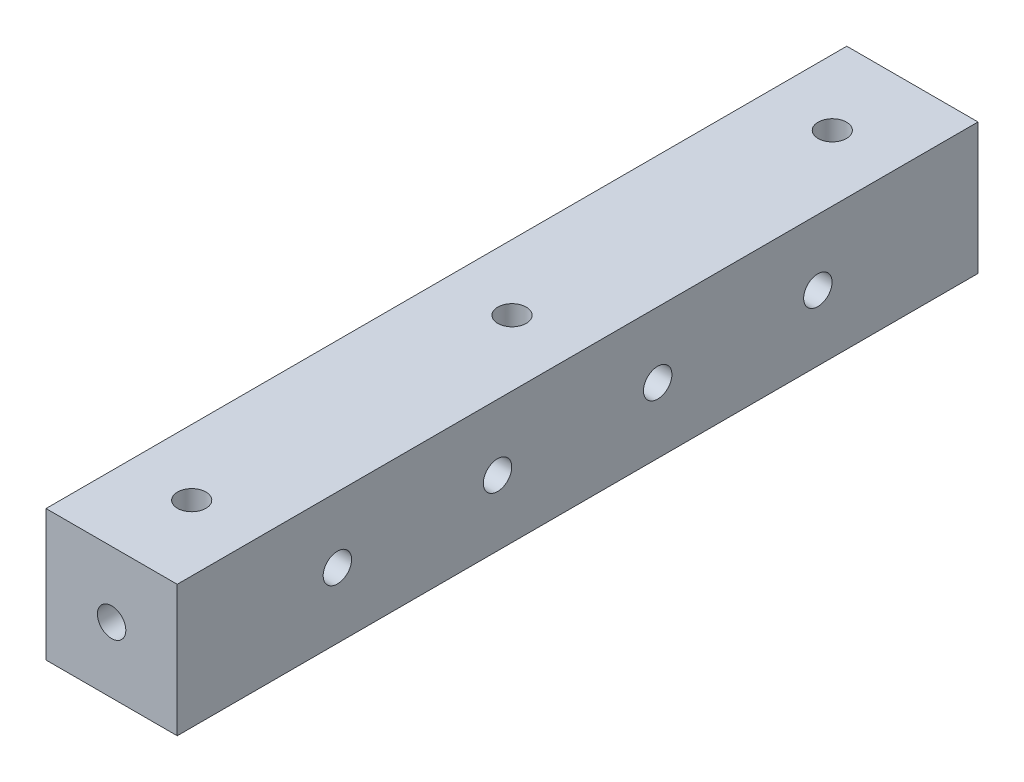
SolidWorks part; units mm, degrees
material "6061 Alloy"
ref_plane "Front Plane" through (0, 0, 0) normal (0, 0, 1) x (1, 0, 0)
ref_plane "Top Plane" through (0, 0, 0) normal (0, 1, 0) x (1, 0, 0)
ref_plane "Right Plane" through (0, 0, 0) normal (1, 0, 0) x (0, 0, -1)
sketch "Sketch1" plane through (0, 0, 0) normal (0, 0, 1) x (1, 0, 0)
  line L1 (-12.7, -12.7) -> (12.7, -12.7)
  line L2 (-12.7, -12.7) -> (-12.7, 12.7)
  line L3 (-12.7, 12.7) -> (12.7, 12.7)
  line L4 (12.7, -12.7) -> (12.7, 12.7)
  line L5 (-12.7, -12.7) -> (12.7, 12.7) construction
  line L6 (-12.7, 12.7) -> (12.7, -12.7) construction
  point P0 (0, 0)
  dimension "D1" = 25.4
extrude "Boss-Extrude1" add sketch "Sketch1" along normal mid plane 155
sketch "Sketch2" plane through (0, 0, 77.5) normal (0, 0, 1) x (1, 0, 0)
  point P0 (0, 0)
sketch "Sketch4" plane through (12.7, 0, 0) normal (1, 0, 0) x (0, 0, -1)
  line L0 (-77.5, -12.7) -> (-77.5, 12.7) construction
  point P0 (-46.5, 0)
  point P1 (-15.5, 0)
  point P2 (15.5, 0)
  point P3 (46.5, 0)
  dimension "D1" = 31
  dimension "D2" = 31
  dimension "D3" = 31
  dimension "D4" = 31
sketch "Sketch5" plane through (0, -12.7, 0) normal (0, -1, 0) x (1, 0, 0)
  line L0 (-12.7, 77.5) -> (12.7, 77.5) construction
  line L1 (-12.7, -77.5) -> (12.7, -77.5) construction
  point P0 (0, 62)
  point P1 (0, 0)
  point P2 (0, -62)
  dimension "D1" = 15.5
  dimension "D2" = 15.5
hole_wizard "M5 Clearance Hole1" positions "Sketch6" profile "Sketch8" hole size "M5" standard "ANSI Metric" end condition through all
sketch "Sketch6" plane through (12.7, 0, 0) normal (1, 0, 0) x (0, 0, -1)
  point P0 (-46.5, 0)
  point P3 (-15.5, 0)
  point P6 (15.5, 0)
  point P9 (46.5, 0)
sketch "Sketch8" plane through (12.7, 0, 46.5) normal (0, 1, 0) x (0, 0, -1)
  line L0 (0, 0) -> (0, 25.4)
  line L1 (0, 25.4) -> (2.75, 25.4)
  line L2 (2.75, 25.4) -> (2.75, 0)
  line L5 (2.75, 0) -> (0, 0)
  line L11 (0, -6.35) -> (0, 107.95) construction
  dimension "Thru Hole Dia." = 5.5
  dimension "Thru Hole Depth" = 25.4
hole_wizard "M5 Clearance Hole2" positions "Sketch9" profile "Sketch10" hole size "M5" standard "ANSI Metric" end condition through all
sketch "Sketch9" plane through (0, -12.7, 0) normal (0, -1, 0) x (-1, 0, 0)
  point P0 (0, -62)
  point P3 (0, 0)
  point P6 (0, 62)
sketch "Sketch10" plane through (0, -12.7, 62) normal (1, 0, 0) x (0, 0, -1)
  line L0 (0, 0) -> (0, 25.4)
  line L1 (0, 25.4) -> (2.75, 25.4)
  line L2 (2.75, 25.4) -> (2.75, 0)
  line L5 (2.75, 0) -> (0, 0)
  line L11 (0, -6.35) -> (0, 107.95) construction
  dimension "Thru Hole Dia." = 5.5
  dimension "Thru Hole Depth" = 25.4
hole_wizard "M5 Clearance Hole3" positions "Sketch11" profile "Sketch12" hole size "M5" standard "ANSI Metric"
sketch "Sketch11" plane through (0, 0, 77.5) normal (0, 0, 1) x (1, 0, 0)
  point P0 (0, 0)
sketch "Sketch12" plane through (0, 0, 77.5) normal (1, 0, 0) x (0, -1, 0)
  line L0 (0, 0) -> (0, 11.6524)
  line L1 (0, 11.6524) -> (2.75, 10)
  line L2 (2.75, 10) -> (2.75, 0)
  line L5 (2.75, 0) -> (0, 0)
  line L10 (0, 11.6524) -> (-2.75, 10) construction
  line L11 (0, -6.35) -> (0, 107.95) construction
  dimension "Hole Dia." = 5.5
  dimension "Hole Depth" = 10
  dimension "Drill Angle" = 118
